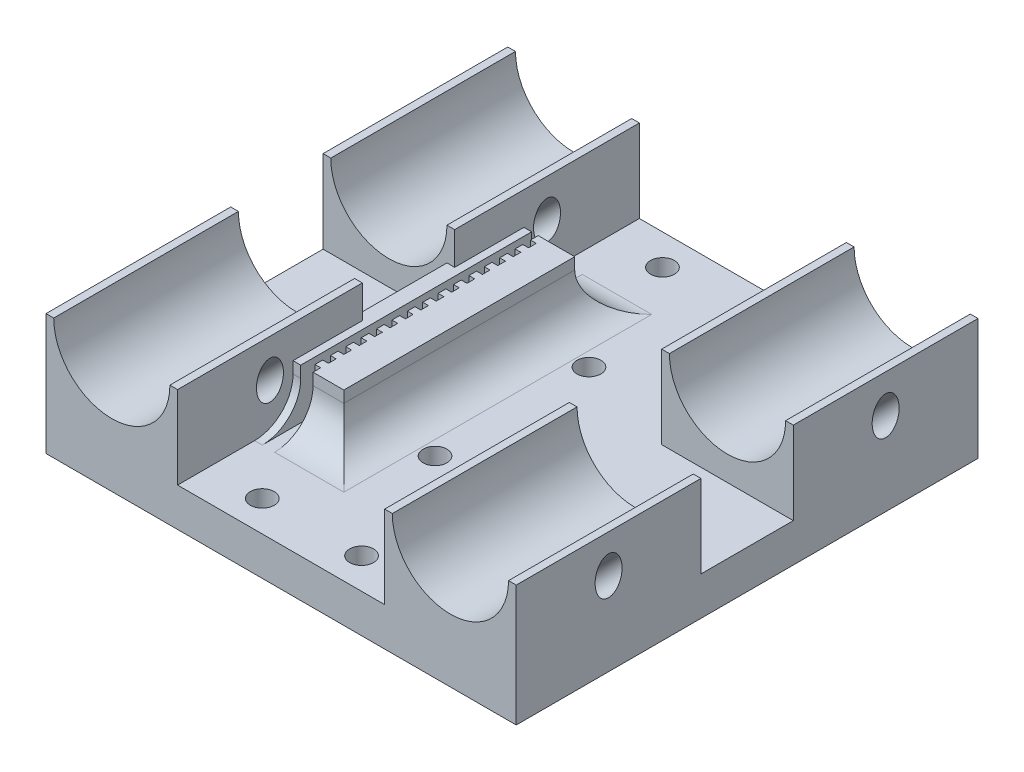
SolidWorks part; units mm, degrees
ref_plane "Front Plane" through (0, 0, 0) normal (0, 0, 1) x (1, 0, 0)
ref_plane "Top Plane" through (0, 0, 0) normal (0, 1, 0) x (1, 0, 0)
ref_plane "Right Plane" through (0, 0, 0) normal (1, 0, 0) x (0, 0, -1)
sketch "Sketch1" plane through (0, 0, 0) normal (0, 1, 0) x (1, 0, 0)
  line L1 (-30.55, 30) -> (30.55, 30)
  line L2 (-30.55, 30) -> (-30.55, -30)
  line L3 (-30.55, -30) -> (30.55, -30)
  line L4 (30.55, 30) -> (30.55, -30)
  dimension "D1" = 60
  dimension "D2" = 61.1
  dimension "D3" = 30.55
  dimension "D4" = 30
extrude "Boss-Extrude1" add sketch "Sketch1" along normal blind 5
sketch "Sketch2" plane through (0, 0, 30) normal (0, 0, 1) x (1, 0, 0)
  line L0 (-30.55, 5) -> (30.55, 5) construction
  line L1 (-30.55, 5) -> (-13.45, 5)
  line L2 (-30.55, 5) -> (-30.55, 15.75)
  line L3 (-30.55, 15.75) -> (-13.45, 15.75)
  line L4 (-13.45, 5) -> (-13.45, 15.75)
  circle A0 centre (-22, 15.75) radius 7.55
  line M3 (30.55, 5) -> (-30.55, 5)
  dimension "D3" = 15.1
  dimension "D1" = 17.1
  dimension "D2" = 10.75
  dimension "D4" = 22
extrude "Boss-Extrude2" add sketch "Sketch2" against normal blind 24 contours A0 L3 L2 L4 M3 region at (-30.348, 10.375, 30)
mirror "Mirror1" about plane through (0, 0, 0) normal (0, 0, 1) of "Boss-Extrude2"
mirror "Mirror2" about plane through (0, 0, 0) normal (1, 0, 0) of "Mirror1"
ref_plane "Plane1" through (-22, 0, 0) normal (-1, 0, 0) x (0, 0, 1)
ref_plane "Plane2" through (-17.775, 17.775, 0) normal (-0.7071, 0.7071, 0) x (0.7071, 0.7071, 0)
sketch "Sketch3" plane through (-17.775, 17.775, 0) normal (-0.7071, 0.7071, 0) x (0.7071, 0.7071, 0)
  line L0 (-10.4652, -30) -> (-21.6021, -30) construction
  line L1 (-10.4652, -6) -> (-10.4652, -30) construction
  circle A0 centre (-13.9652, -18) radius 1.75
  dimension "D1" = 3.5
  dimension "D2" = 12
  dimension "D3" = 3.5
extrude "Cut-Extrude1" cut sketch "Sketch3" against normal through all both and the other way through all
mirror "Mirror3" about plane through (-22, 0, 0) normal (-1, 0, 0) of "Cut-Extrude1"
mirror "Mirror4" about plane through (0, 0, 0) normal (0, 0, 1) of "Mirror3", "Cut-Extrude1"
mirror "Mirror5" about plane through (0, 0, 0) normal (1, 0, 0) of "Mirror4", "Cut-Extrude1", "Mirror3"
sketch "Sketch10" plane through (0, 5, 0) normal (0, 1, 0) x (1, 0, 0)
  line L1 (13.45, 30) -> (-13.45, 30) construction
  line L4 (-13.45, -30) -> (13.45, -30) construction
  line L5 (-13.45, -6) -> (-13.45, -30) construction
  line L6 (13.45, 6) -> (13.45, 30) construction
  circle A0 centre (-6.45, -26) radius 1.55
  circle A1 centre (-6.45, 26) radius 1.55
  circle A2 centre (6.45, 26) radius 1.55
  circle A3 centre (6.45, -26) radius 1.55
  dimension "D1" = 3.1
  dimension "D2" = 7
  dimension "D3" = 4
  dimension "D4" = 4
  dimension "D7" = 4
  dimension "D8" = 7
  dimension "D9" = 4
extrude "Cut-Extrude7" cut sketch "Sketch10" against normal blind 8
sketch "Sketch11" plane through (0, 0, 0) normal (0, -1, 0) x (1, 0, 0)
  circle A0 centre (-6.45, 26) radius 3
  circle A1 centre (6.45, 26) radius 3
  circle A2 centre (6.45, -26) radius 3
  circle A3 centre (-6.45, -26) radius 3
  dimension "D1" = 6
extrude "Cut-Extrude8" cut sketch "Sketch11" against normal blind 1
sketch "Sketch12" plane through (0, 5, 0) normal (0, 1, 0) x (1, 0, 0)
  line L1 (-10.85, 15) -> (-6.85, 15)
  line L2 (-10.85, 15) -> (-10.85, -15)
  line L3 (-10.85, -15) -> (-6.85, -15)
  line L4 (-6.85, 15) -> (-6.85, -15)
  line L5 (-10.85, 15) -> (-11.6, 15)
  line L6 (-10.85, 15) -> (-10.85, 14)
  line L7 (-10.85, 14) -> (-11.6, 14)
  line L8 (-11.6, 15) -> (-11.6, 14)
  line L20 (-13.45, -6) -> (-13.45, -30) construction
  line L21 (-14.45, 15) -> (-12.45, 15)
  line L22 (-14.45, 15) -> (-14.45, -15)
  line L23 (-14.45, -15) -> (-12.45, -15)
  line L24 (-12.45, 15) -> (-12.45, -15)
  line L25 (13.45, 30) -> (-13.45, 30) construction
  dimension "D1" = 4
  dimension "D2" = 30
  dimension "D3" = 1
  dimension "D4" = 0.75
  dimension "D6" = 1.6
  dimension "D7" = 2
  dimension "D8" = 1
  dimension "D11" = 15
extrude "Boss-Extrude5" add sketch "Sketch12" along normal blind 6.5 contours L24 L21 L22 L23 | L4 L1 L2 L3 region at (-8.85, 5, 0) region at (-13.45, 5, 0)
fillet "Fillet1" radius 5 6 edges at (-8.85, 5, 15) (-6.85, 5, 0) (-8.85, 5, -15) (-12.95, 5, -15) (-14.45, 5, 0) (-12.95, 5, 15)
extrude "Boss-Extrude6" add sketch "Sketch12<4>" along normal blind 6.5 contours L5 L8 L7 L2 region at (-11.225, 5, -14.5)
sketch "Sketch12<4>" plane through (0, 5, 0) normal (0, 1, 0) x (1, 0, 0) same geometry as "Sketch12"
pattern_linear "LPattern1" count 15 spacing 2 along (0, 0, 1) of "Boss-Extrude6"
sketch "Sketch13" plane through (0, 0, 0) normal (0, -1, 0) x (1, 0, 0)
  circle A0 centre (0, 10) radius 1.55
  circle A1 centre (0, -10) radius 1.55
  dimension "D3" = 3.1
  dimension "D1" = 20
  dimension "D2" = 10
extrude "Cut-Extrude9" cut sketch "Sketch13" against normal blind 6.5
